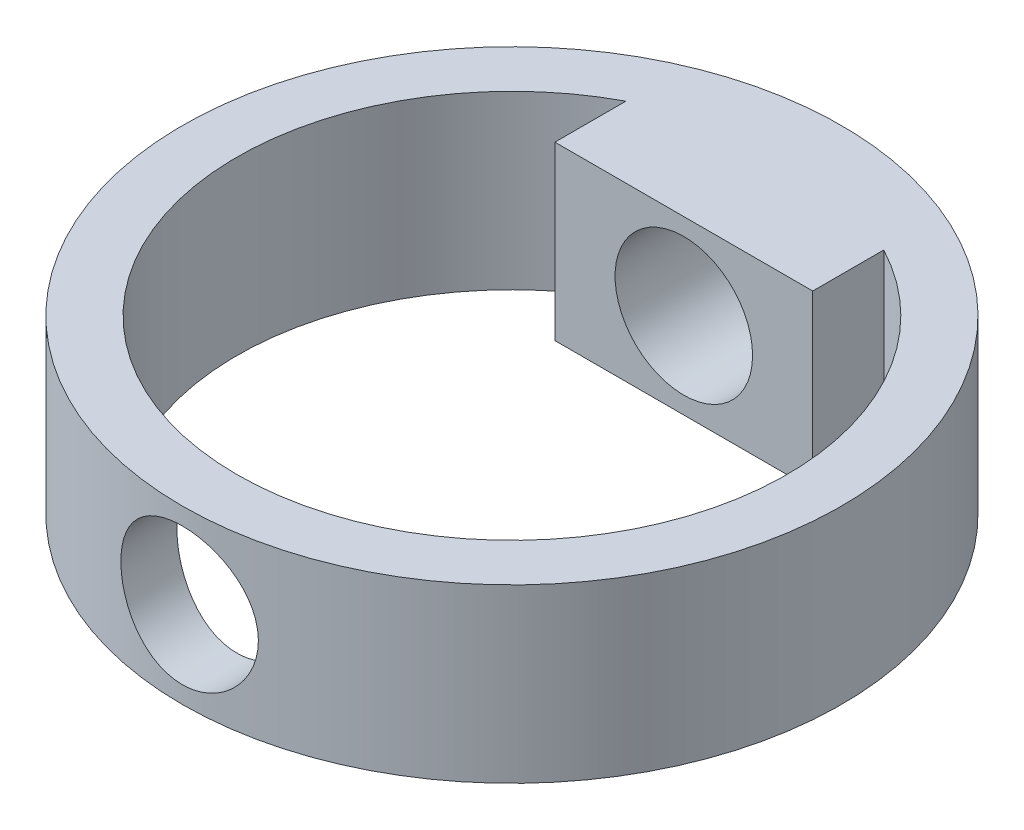
SolidWorks part; units mm, degrees
ref_plane "Top Plane" through (0, 0, 0) normal (0, 0, 1) x (1, 0, 0)
ref_plane "Right Plane" through (0, 0, 0) normal (0, 1, 0) x (1, 0, 0)
ref_plane "Front Plane" through (0, 0, 0) normal (1, 0, 0) x (0, 0, -1)
ref_axis "x-axis" through (-88.99, 0, 0) along (1, 0, 0)
ref_axis "y-axis" through (0, -55, 0) along (0, 1, 0)
ref_axis "z-axis" through (0, 0, 55) along (0, 0, -1)
sketch "Sketch6" plane through (0, 0, 0) normal (0, 1, 0) x (1, 0, 0)
  circle A0 centre (0, 0) radius 16
  circle A1 centre (0, 0) radius 19.175
  dimension "D1" = 3.175
  dimension "D2" = 32
extrude "Boss-Extrude4" add sketch "Sketch6" along normal mid plane 10
ref_plane "Plane3" through (0, 0, 3.7) normal (0, 0, 1) x (1, 0, 0)
sketch "Sketch7" plane through (0, 0, 3.7) normal (0, 0, 1) x (1, 0, 0)
  circle A0 centre (0, 0) radius 4
  dimension "D1" = 8
extrude "Boss-Extrude5" [suppressed] add sketch "Sketch7" against normal up to next
ref_plane "Plane2" through (0, 0, -10) normal (0, 0, 1) x (1, 0, 0)
sketch "Sketch8" plane through (0, 0, -10) normal (0, 0, 1) x (1, 0, 0)
  line L0 (16, 5) -> (-16, 5) construction
  line L1 (-7.5, 5) -> (7.5, 5)
  line L2 (-7.5, 5) -> (-7.5, -5)
  line L3 (-7.5, -5) -> (7.5, -5)
  line L4 (7.5, 5) -> (7.5, -5)
  line L5 (-7.5, 5) -> (7.5, -5) construction
  line L6 (-7.5, -5) -> (7.5, 5) construction
  point P0 (0, 0)
  dimension "D1" = 15
extrude "Boss-Extrude6" add sketch "Sketch8" against normal up to next
extrude "Cut-Extrude1" cut sketch "Sketch7<2>" against normal through all both and the other way through all
sketch "Sketch7<2>" plane through (0, 0, 3.7) normal (0, 0, 1) x (1, 0, 0) same geometry as "Sketch7"
